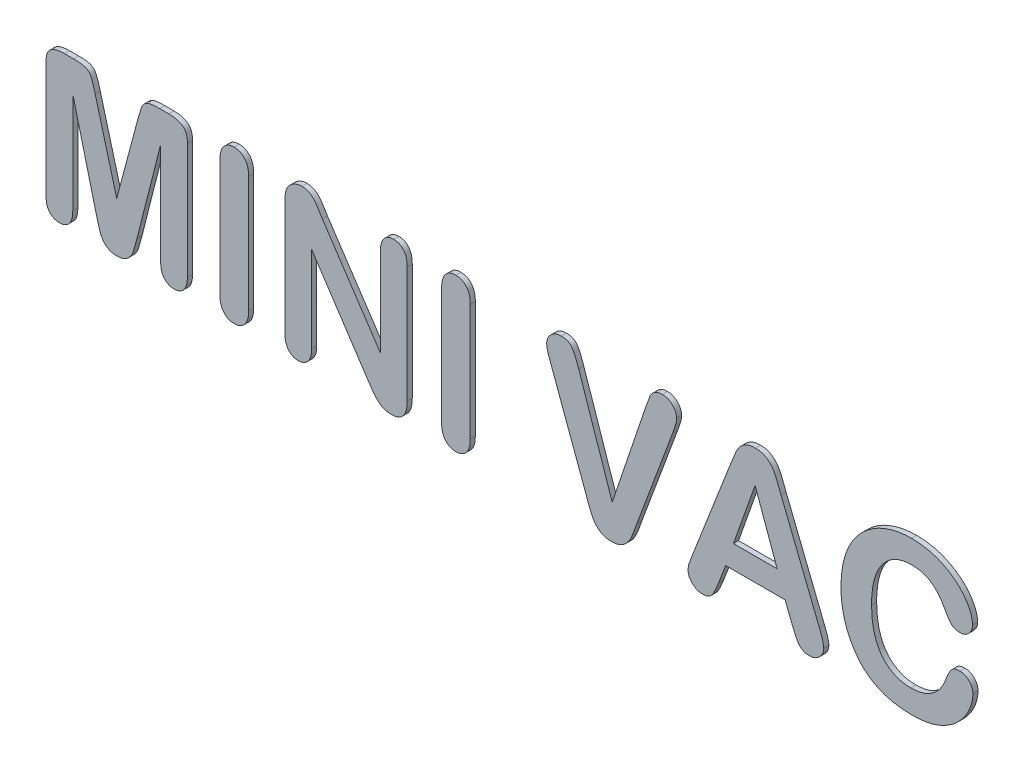
SolidWorks part; units mm, degrees
ref_plane "Front" through (0, 0, 0) normal (0, 0, 1) x (1, 0, 0)
ref_plane "Top" through (0, 0, 0) normal (0, 1, 0) x (1, 0, 0)
ref_plane "Right" through (0, 0, 0) normal (1, 0, 0) x (0, 0, -1)
sketch "Sketch1" plane through (0, 0, 0) normal (0, 0, 1) x (1, 0, 0)
  line L1 (-70.9822, -5) -> (70.9822, -5) construction
  line L2 (-70.9822, -5) -> (-70.9822, 5) construction
  line L3 (-70.9822, 5) -> (70.9822, 5) construction
  line L4 (70.9822, -5) -> (70.9822, 5) construction
  line L5 (-70.9822, -5) -> (70.9822, 5) construction
  line L6 (-70.9822, 5) -> (70.9822, -5) construction
  text T0 "MAXWELL SAVINGS"
  point P0 (0, 0)
  dimension "D1" = 10
extrude "Boss-Extrude1" [suppressed] add sketch "Sketch1" against normal blind 0.99 and the other way blind 0.01
sketch "Sketch2" [suppressed] plane through (0, 0, 0) normal (0, 0, 1) x (1, 0, 0)
  line L1 (-49.8033, -12.5) -> (49.8033, -12.5) construction
  line L2 (-49.8033, -12.5) -> (-49.8033, 12.5) construction
  line L3 (-49.8033, 12.5) -> (49.8033, 12.5) construction
  line L4 (49.8033, -12.5) -> (49.8033, 12.5) construction
  line L5 (-49.8033, -12.5) -> (49.8033, 12.5) construction
  line L6 (-49.8033, 12.5) -> (49.8033, -12.5) construction
  text T0 "LCDs" font "Arial Rounded MT Bold" height 25
  point P0 (0, 0)
  dimension "D1" = 25
extrude "Boss-Extrude2" [suppressed] add sketch "Sketch2" along normal blind 0.01 and the other way blind 0.99
sketch "Sketch3" [suppressed] plane through (0, 0, 0) normal (0, 0, 1) x (1, 0, 0)
  line L0 (0, 0) -> (0, -12) construction
  line L1 (-74.5704, 5) -> (74.5704, 5) construction
  line L2 (-74.5704, 5) -> (-74.5704, -5) construction
  line L3 (-74.5704, -5) -> (74.5704, -5) construction
  line L4 (74.5704, 5) -> (74.5704, -5) construction
  line L5 (-74.5704, 5) -> (74.5704, -5) construction
  line L6 (-74.5704, -5) -> (74.5704, 5) construction
  line L7 (-93.4233, -17) -> (93.4233, -17) construction
  line L8 (-93.4233, -17) -> (-93.4233, -7) construction
  line L9 (-93.4233, -7) -> (93.4233, -7) construction
  line L10 (93.4233, -17) -> (93.4233, -7) construction
  line L11 (-93.4233, -17) -> (93.4233, -7) construction
  line L12 (-93.4233, -7) -> (93.4233, -17) construction
  line L13 (0, -24) -> (0, -12) construction
  line L14 (-98.5214, -19) -> (98.5214, -19) construction
  line L15 (-98.5214, -19) -> (-98.5214, -29) construction
  line L16 (-98.5214, -29) -> (98.5214, -29) construction
  line L17 (98.5214, -19) -> (98.5214, -29) construction
  line L18 (-98.5214, -19) -> (98.5214, -29) construction
  line L19 (-98.5214, -29) -> (98.5214, -19) construction
  line L20 (0, -24) -> (0, -36) construction
  line L21 (-96.3145, -41) -> (96.3145, -41) construction
  line L22 (-96.3145, -41) -> (-96.3145, -31) construction
  line L23 (-96.3145, -31) -> (96.3145, -31) construction
  line L24 (96.3145, -41) -> (96.3145, -31) construction
  line L25 (-96.3145, -41) -> (96.3145, -31) construction
  line L26 (-96.3145, -31) -> (96.3145, -41) construction
  line L27 (-90.4498, -53) -> (90.4498, -53) construction
  line L28 (-90.4498, -53) -> (-90.4498, -43) construction
  line L29 (-90.4498, -43) -> (90.4498, -43) construction
  line L30 (90.4498, -53) -> (90.4498, -43) construction
  line L31 (-90.4498, -53) -> (90.4498, -43) construction
  line L32 (-90.4498, -43) -> (90.4498, -53) construction
  line L33 (0, -36) -> (0, -48) construction
  line L34 (0, -48) -> (0, -60) construction
  line L35 (-89.3662, -65) -> (89.3662, -65) construction
  line L36 (-89.3662, -65) -> (-89.3662, -55) construction
  line L37 (-89.3662, -55) -> (89.3662, -55) construction
  line L38 (89.3662, -65) -> (89.3662, -55) construction
  line L39 (-89.3662, -65) -> (89.3662, -55) construction
  line L40 (-89.3662, -55) -> (89.3662, -65) construction
  line L41 (-102.5842, -77) -> (102.5842, -77) construction
  line L42 (-102.5842, -77) -> (-102.5842, -67) construction
  line L43 (-102.5842, -67) -> (102.5842, -67) construction
  line L44 (102.5842, -77) -> (102.5842, -67) construction
  line L45 (-102.5842, -77) -> (102.5842, -67) construction
  line L46 (-102.5842, -67) -> (102.5842, -77) construction
  line L47 (-89.9079, -89) -> (89.9079, -89) construction
  line L48 (-89.9079, -89) -> (-89.9079, -79) construction
  line L49 (-89.9079, -79) -> (89.9079, -79) construction
  line L50 (89.9079, -89) -> (89.9079, -79) construction
  line L51 (-89.9079, -89) -> (89.9079, -79) construction
  line L52 (-89.9079, -79) -> (89.9079, -89) construction
  line L53 (-71.8145, -101) -> (71.8145, -101) construction
  line L54 (-71.8145, -101) -> (-71.8145, -91) construction
  line L55 (-71.8145, -91) -> (71.8145, -91) construction
  line L56 (71.8145, -101) -> (71.8145, -91) construction
  line L57 (-71.8145, -101) -> (71.8145, -91) construction
  line L58 (-71.8145, -91) -> (71.8145, -101) construction
  line L59 (0, -60) -> (0, -72) construction
  line L60 (0, -72) -> (0, -84) construction
  line L61 (0, -84) -> (0, -96) construction
  line L62 (0, -96) -> (0, -108) construction
  line L63 (-67.281, -113) -> (67.281, -113) construction
  line L64 (-67.281, -113) -> (-67.281, -103) construction
  line L65 (-67.281, -103) -> (67.281, -103) construction
  line L66 (67.281, -113) -> (67.281, -103) construction
  line L67 (-67.281, -113) -> (67.281, -103) construction
  line L68 (-67.281, -103) -> (67.281, -113) construction
  line L69 (-48.938, -125) -> (48.938, -125) construction
  line L70 (-48.938, -125) -> (-48.938, -115) construction
  line L71 (-48.938, -115) -> (48.938, -115) construction
  line L72 (48.938, -125) -> (48.938, -115) construction
  line L73 (-48.938, -125) -> (48.938, -115) construction
  line L74 (-48.938, -115) -> (48.938, -125) construction
  line L75 (-50.7146, -137) -> (50.7146, -137) construction
  line L76 (-50.7146, -137) -> (-50.7146, -127) construction
  line L77 (-50.7146, -127) -> (50.7146, -127) construction
  line L78 (50.7146, -137) -> (50.7146, -127) construction
  line L79 (-50.7146, -137) -> (50.7146, -127) construction
  line L80 (-50.7146, -127) -> (50.7146, -137) construction
  line L81 (-67.281, -149) -> (67.281, -149) construction
  line L82 (-67.281, -149) -> (-67.281, -139) construction
  line L83 (-67.281, -139) -> (67.281, -139) construction
  line L84 (67.281, -149) -> (67.281, -139) construction
  line L85 (-67.281, -149) -> (67.281, -139) construction
  line L86 (-67.281, -139) -> (67.281, -149) construction
  line L87 (0, -108) -> (0, -120) construction
  line L88 (0, -120) -> (0, -132) construction
  line L89 (0, -132) -> (0, -144) construction
  text T0 "A SCOUT IS:"
  text T1 "TRUSTWORTHY"
  text T2 "LOYAL"
  text T3 "HELPFUL"
  text T4 "FRIENDLY"
  text T5 "COURTEOUS"
  text T6 "KIND"
  text T7 "OBEDIENT"
  text T8 "CHEERFUL"
  text T9 "THRIFTY"
  text T10 "BRAVE"
  text T11 "CLEAN"
  text T12 "REVERENT"
  point P0 (0, 0)
  point P8 (0, -24)
  point P9 (0, -12)
  point P21 (0, -36)
  point P26 (0, -48)
  point P34 (0, -60)
  point P39 (0, -72)
  point P44 (0, -84)
  point P49 (0, -96)
  point P61 (0, -108)
  point P66 (0, -120)
  point P71 (0, -132)
  point P76 (0, -144)
  dimension "D1" = 10
  dimension "D2" = 12
extrude "Scout Law" [suppressed] add sketch "Sketch3" against normal blind 1
sketch "Sketch4" [suppressed] plane through (0, 0, 0) normal (0, 0, 1) x (1, 0, 0)
  line L1 (-39.3198, -5.138) -> (39.3198, -5.138) construction
  line L2 (-39.3198, -5.138) -> (-39.3198, 5.138) construction
  line L3 (-39.3198, 5.138) -> (39.3198, 5.138) construction
  line L4 (39.3198, -5.138) -> (39.3198, 5.138) construction
  line L5 (-39.3198, -5.138) -> (39.3198, 5.138) construction
  line L6 (-39.3198, 5.138) -> (39.3198, -5.138) construction
  text T0 "TROOP 159"
  point P0 (0, 0)
extrude "Troop 159" [suppressed] add sketch "Sketch4" against normal blind 1
sketch "Sketch5" [suppressed] plane through (0, 0, 0) normal (0, 0, 1) x (1, 0, 0)
  line L0 (0, -24) -> (0, -12) construction
  line L1 (-100.0649, -5) -> (100.0649, -5) construction
  line L2 (-100.0649, -5) -> (-100.0649, 5) construction
  line L3 (-100.0649, 5) -> (100.0649, 5) construction
  line L4 (100.0649, -5) -> (100.0649, 5) construction
  line L5 (-100.0649, -5) -> (100.0649, 5) construction
  line L6 (-100.0649, 5) -> (100.0649, -5) construction
  line L7 (-94.2614, -17) -> (94.2614, -17) construction
  line L8 (-94.2614, -17) -> (-94.2614, -7) construction
  line L9 (-94.2614, -7) -> (94.2614, -7) construction
  line L10 (94.2614, -17) -> (94.2614, -7) construction
  line L11 (-94.2614, -17) -> (94.2614, -7) construction
  line L12 (-94.2614, -7) -> (94.2614, -17) construction
  line L13 (-51.9196, -29) -> (51.9196, -29) construction
  line L14 (-51.9196, -29) -> (-51.9196, -19) construction
  line L15 (-51.9196, -19) -> (51.9196, -19) construction
  line L16 (51.9196, -29) -> (51.9196, -19) construction
  line L17 (-51.9196, -29) -> (51.9196, -19) construction
  line L18 (-51.9196, -19) -> (51.9196, -29) construction
  line L19 (0, -12) -> (0, 0) construction
  text T0 "MAXWELL"
  text T1 "AINSWORTH"
  text T2 "TROOP 159"
  point P0 (0, 0)
  point P6 (0, -12)
  point P12 (0, -24)
  dimension "D1" = 10
  dimension "D2" = 12
extrude "Maxwell Ainsworth Troop 159" [suppressed] add sketch "Sketch5" against normal blind 1
sketch "Sketch6" [suppressed] plane through (0, 0, 0) normal (0, 0, 1) x (1, 0, 0)
  line L0 (0, 0) -> (0, -12) construction
  line L1 (-75.3315, -5) -> (75.3315, -5) construction
  line L2 (-75.3315, -5) -> (-75.3315, 5) construction
  line L3 (-75.3315, 5) -> (75.3315, 5) construction
  line L4 (75.3315, -5) -> (75.3315, 5) construction
  line L5 (-75.3315, -5) -> (75.3315, 5) construction
  line L6 (-75.3315, 5) -> (75.3315, -5) construction
  line L7 (-89.4225, -17) -> (89.4225, -17) construction
  line L8 (-89.4225, -17) -> (-89.4225, -7) construction
  line L9 (-89.4225, -7) -> (89.4225, -7) construction
  line L10 (89.4225, -17) -> (89.4225, -7) construction
  line L11 (-89.4225, -17) -> (89.4225, -7) construction
  line L12 (-89.4225, -7) -> (89.4225, -17) construction
  line L13 (-63.2822, -29) -> (63.2822, -29) construction
  line L14 (-63.2822, -29) -> (-63.2822, -19) construction
  line L15 (-63.2822, -19) -> (63.2822, -19) construction
  line L16 (63.2822, -29) -> (63.2822, -19) construction
  line L17 (-63.2822, -29) -> (63.2822, -19) construction
  line L18 (-63.2822, -19) -> (63.2822, -29) construction
  line L19 (-99.3833, -41) -> (99.3833, -41) construction
  line L20 (-99.3833, -41) -> (-99.3833, -31) construction
  line L21 (-99.3833, -31) -> (99.3833, -31) construction
  line L22 (99.3833, -41) -> (99.3833, -31) construction
  line L23 (-99.3833, -41) -> (99.3833, -31) construction
  line L24 (-99.3833, -31) -> (99.3833, -41) construction
  line L25 (-107.9526, -53) -> (107.9526, -53) construction
  line L26 (-107.9526, -53) -> (-107.9526, -43) construction
  line L27 (-107.9526, -43) -> (107.9526, -43) construction
  line L28 (107.9526, -53) -> (107.9526, -43) construction
  line L29 (-107.9526, -53) -> (107.9526, -43) construction
  line L30 (-107.9526, -43) -> (107.9526, -53) construction
  line L31 (0, -12) -> (0, -24) construction
  line L32 (0, -24) -> (0, -36) construction
  line L33 (0, -36) -> (0, -48) construction
  line L34 (0, -48) -> (0, -60) construction
  line L35 (-102.02, -65) -> (102.02, -65) construction
  line L36 (-102.02, -65) -> (-102.02, -55) construction
  line L37 (-102.02, -55) -> (102.02, -55) construction
  line L38 (102.02, -65) -> (102.02, -55) construction
  line L39 (-102.02, -65) -> (102.02, -55) construction
  line L40 (-102.02, -55) -> (102.02, -65) construction
  line L41 (-97.9331, -77) -> (97.9331, -77) construction
  line L42 (-97.9331, -77) -> (-97.9331, -67) construction
  line L43 (-97.9331, -67) -> (97.9331, -67) construction
  line L44 (97.9331, -77) -> (97.9331, -67) construction
  line L45 (-97.9331, -77) -> (97.9331, -67) construction
  line L46 (-97.9331, -67) -> (97.9331, -77) construction
  line L47 (-112.1713, -89) -> (112.1713, -89) construction
  line L48 (-112.1713, -89) -> (-112.1713, -79) construction
  line L49 (-112.1713, -79) -> (112.1713, -79) construction
  line L50 (112.1713, -89) -> (112.1713, -79) construction
  line L51 (-112.1713, -89) -> (112.1713, -79) construction
  line L52 (-112.1713, -79) -> (112.1713, -89) construction
  line L53 (0, -60) -> (0, -72) construction
  line L54 (0, -72) -> (0, -84) construction
  line L55 (0, -84) -> (0, -96) construction
  line L56 (-115.8476, -101) -> (115.8476, -101) construction
  line L57 (-115.8476, -101) -> (-115.8476, -91) construction
  line L58 (-115.8476, -91) -> (115.8476, -91) construction
  line L59 (115.8476, -101) -> (115.8476, -91) construction
  line L60 (-115.8476, -101) -> (115.8476, -91) construction
  line L61 (-115.8476, -91) -> (115.8476, -101) construction
  line L62 (-110.6686, -113) -> (110.6686, -113) construction
  line L63 (-110.6686, -113) -> (-110.6686, -103) construction
  line L64 (-110.6686, -103) -> (110.6686, -103) construction
  line L65 (110.6686, -113) -> (110.6686, -103) construction
  line L66 (-110.6686, -113) -> (110.6686, -103) construction
  line L67 (-110.6686, -103) -> (110.6686, -113) construction
  line L68 (-111.9241, -125) -> (111.9241, -125) construction
  line L69 (-111.9241, -125) -> (-111.9241, -115) construction
  line L70 (-111.9241, -115) -> (111.9241, -115) construction
  line L71 (111.9241, -125) -> (111.9241, -115) construction
  line L72 (-111.9241, -125) -> (111.9241, -115) construction
  line L73 (-111.9241, -115) -> (111.9241, -125) construction
  line L74 (0, -96) -> (0, -108) construction
  line L75 (0, -108) -> (0, -120) construction
  line L76 (0, -120) -> (0, -132) construction
  line L77 (-107.9526, -137) -> (107.9526, -137) construction
  line L78 (-107.9526, -137) -> (-107.9526, -127) construction
  line L79 (-107.9526, -127) -> (107.9526, -127) construction
  line L80 (107.9526, -137) -> (107.9526, -127) construction
  line L81 (-107.9526, -137) -> (107.9526, -127) construction
  line L82 (-107.9526, -127) -> (107.9526, -137) construction
  text T0 "ON MY HONOR"
  text T1 "I WILL DO MY BEST"
  text T2 "TO DO MY DUTY"
  text T3 "TO GOD AND MY"
  text T4 "COUNTRY AND TO"
  text T5 "OBEY THE SCOUT LAW;"
  text T6 "TO HELP OTHER PEOPLE"
  text T7 "AT ALL TIMES; TO KEEP"
  text T8 "MYSELF PHYSICALLY"
  text T9 "STRONG, MENTALLY"
  text T10 "AWAKE, AND"
  text T11 "MORALLY STRAIGHT"
  point P0 (0, 0)
  point P6 (0, -12)
  point P12 (0, -24)
  point P17 (0, -36)
  point P22 (0, -48)
  point P34 (0, -60)
  point P39 (0, -72)
  point P44 (0, -84)
  point P50 (0, -96)
  point P58 (0, -108)
  point P63 (0, -120)
  point P69 (0, -132)
  dimension "D1" = 10
  dimension "D2" = 12
extrude "Scout Oath" [suppressed] add sketch "Sketch6" against normal blind 1
sketch "Sketch7" plane through (0, 0, 0) normal (0, 0, 1) x (1, 0, 0)
  line L1 (-140.4264, -15) -> (140.4264, -15) construction
  line L2 (-140.4264, -15) -> (-140.4264, 15) construction
  line L3 (-140.4264, 15) -> (140.4264, 15) construction
  line L4 (140.4264, -15) -> (140.4264, 15) construction
  line L5 (-140.4264, -15) -> (140.4264, 15) construction
  line L6 (-140.4264, 15) -> (140.4264, -15) construction
  text T0 "MINI VAC" font "Arial Rounded MT Bold" height 30
  point P0 (0, 0)
  dimension "D1" = 30
extrude "Mini Vac" add sketch "Sketch7" along normal blind 1
